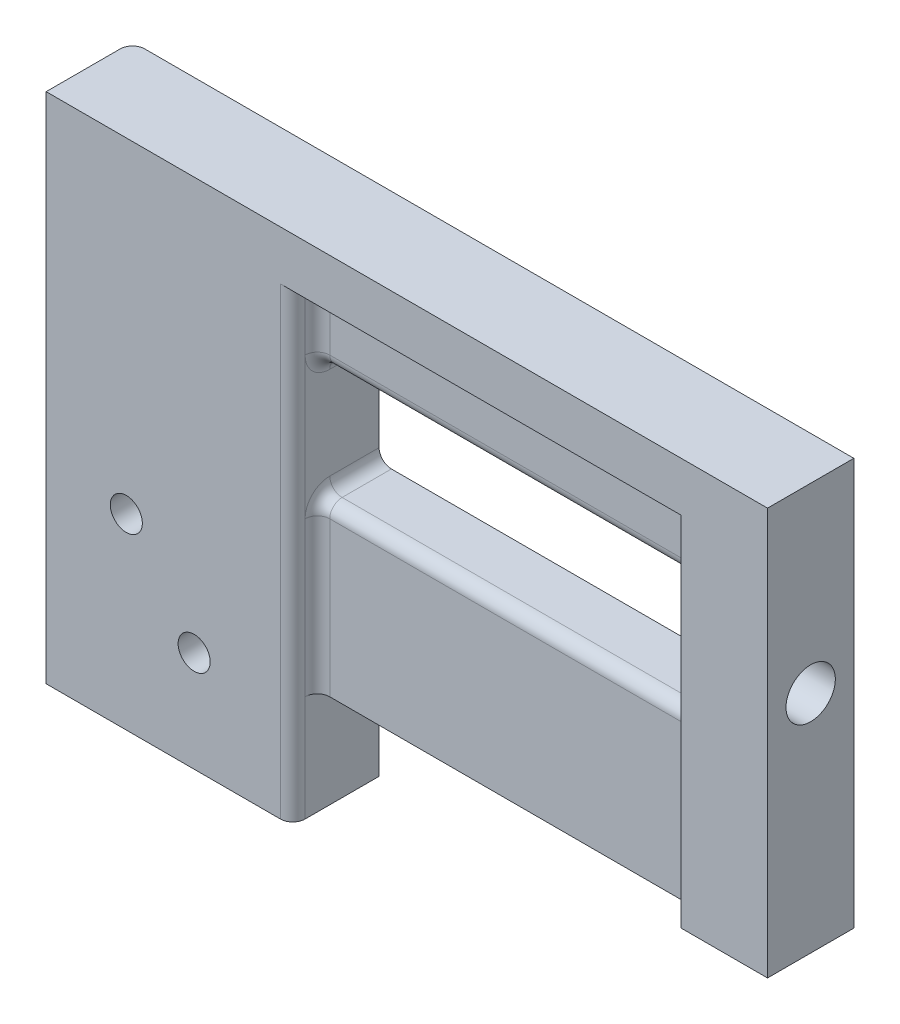
SolidWorks part; units mm, degrees
ref_plane "Front Plane" through (0, 0, 0) normal (0, 0, 1) x (1, 0, 0)
ref_plane "Top Plane" through (0, 0, 0) normal (0, 1, 0) x (1, 0, 0)
ref_plane "Right Plane" through (0, 0, 0) normal (1, 0, 0) x (0, 0, -1)
sketch "Sketch1" plane through (0, 0, 0) normal (0, 0, 1) x (1, 0, 0)
  line L1 (-15.75, -13.5) -> (22.75, -13.5)
  line L3 (-15.75, 19.5) -> (22.75, 19.5)
  line L4 (22.75, -13.5) -> (22.75, 19.5)
  line L5 (20.5, 0) -> (15.75, 0) construction
  line L7 (-15.75, 0) -> (15.75, 0)
  line L9 (-15.75, 9.5) -> (15.75, 9.5)
  line L10 (15.75, 0) -> (15.75, 9.5)
  line L12 (-15.75, 19.5) -> (-19.75, 19.5)
  line L13 (-15.75, 9.5) -> (-15.75, 0)
  line L14 (-15.75, -13.5) -> (-19.75, -13.5)
  line L15 (-19.75, 19.5) -> (-19.75, -13.5)
  point P0 (0, 0)
extrude "Boss-Extrude1" add sketch "Sketch1" along normal blind 5
sketch "Sketch2" plane through (0, 0, 0) normal (0, 0, 1) x (1, 0, 0)
  line L0 (22.75, 19.5) -> (-19.75, 19.5) construction
  line L5 (-15.75, 19.5) -> (-35.75, 19.5)
  line L6 (-15.75, 15.5) -> (-15.75, -13.5)
  line L8 (-35.75, 19.5) -> (-35.75, -13.5)
  line L9 (22.75, -13.5) -> (16.5977, -13.5)
  line L10 (22.75, -13.5) -> (22.75, 19.5)
  line L11 (22.75, 19.5) -> (15.7561, 19.5)
  line L13 (15.75, 0) -> (15.75, 15.5)
  line L14 (-15.75, 15.5) -> (15.75, 15.5)
  line L16 (-15.75, 19.5) -> (15.7561, 19.5)
  line L18 (15.75, 0) -> (15.75, -13.5)
  line L19 (-19.75, -13.5) -> (22.75, -13.5) construction
  line L20 (15.75, -13.5) -> (16.5977, -13.5)
  line L21 (-25.75, 19.5) -> (-25.75, 3.3125) construction
  line L22 (-25.75, 3.3125) -> (-25.75, -22.0875) construction
  line L23 (-35.75, -13.5) -> (-35.75, -22.0875)
  line L24 (-35.75, -22.0875) -> (-15.75, -22.0875)
  line L25 (-15.75, -22.0875) -> (-15.75, -13.5)
extrude "Boss-Extrude2" add sketch "Sketch2" along normal blind 7
sketch "Sketch4" plane through (0, 0, 0) normal (1, 0, 0) x (0, 0, -1)
  line L0 (0, 4.75) -> (-7, 4.75) construction
  line L2 (-7, -13.5) -> (-7, 19.5) construction
  circle A0 centre (-3.5, 4.75) radius 2
extrude "Cut-Extrude1" cut sketch "Sketch4" against normal blind 7 from surface starting at face at (22.75, 3, 3.5)
sketch "Sketch5" plane through (0, 0, 0) normal (0, 0, 1) x (1, 0, 0)
  line L0 (-35.75, 19.5) -> (-35.75, -10.41) construction
  line L2 (-25.25, 6.8) -> (-27.75, 6.8) construction
  line L4 (-22.25, 6.8) -> (-19.75, 6.8) construction
  line L5 (-35.75, 19.5) -> (-35.75, -22.0875) construction
  line L6 (-22.25, 6.8) -> (-25.25, 6.8) construction
  line L7 (-27.75, 6.8) -> (-30.75, 6.8) construction
  line L8 (-30.75, 6.8) -> (-35.75, 6.8) construction
  line L11 (-19.75, 6.8) -> (-15.75, 6.8) construction
  line L13 (-35.75, -10.41) -> (-15.75, -10.41) construction
  line L14 (-15.75, -13.5) -> (-15.75, 0) construction
  line L15 (-29.25, -10.41) -> (-29.25, -6.91) construction
  line L16 (-23.75, -10.41) -> (-23.75, -13.91) construction
  circle A2 centre (-23.75, -13.91) radius 1.3
  circle A3 centre (-29.25, -6.91) radius 1.3
extrude "Cut-Extrude2" cut sketch "Sketch5" along normal blind 7
fillet "Fillet2" radius 1 9 edges at (-15.75, -6.75, 5) (0, 15.5, 5) (-15.75, 12.5, 5) (-15.75, 0, 2.5) (-15.75, 9.5, 2.5) (-15.75, -3.2937, 7) (0, 0, 5) (0, 9.5, 5) (-35.75, -1.2937, 0)
